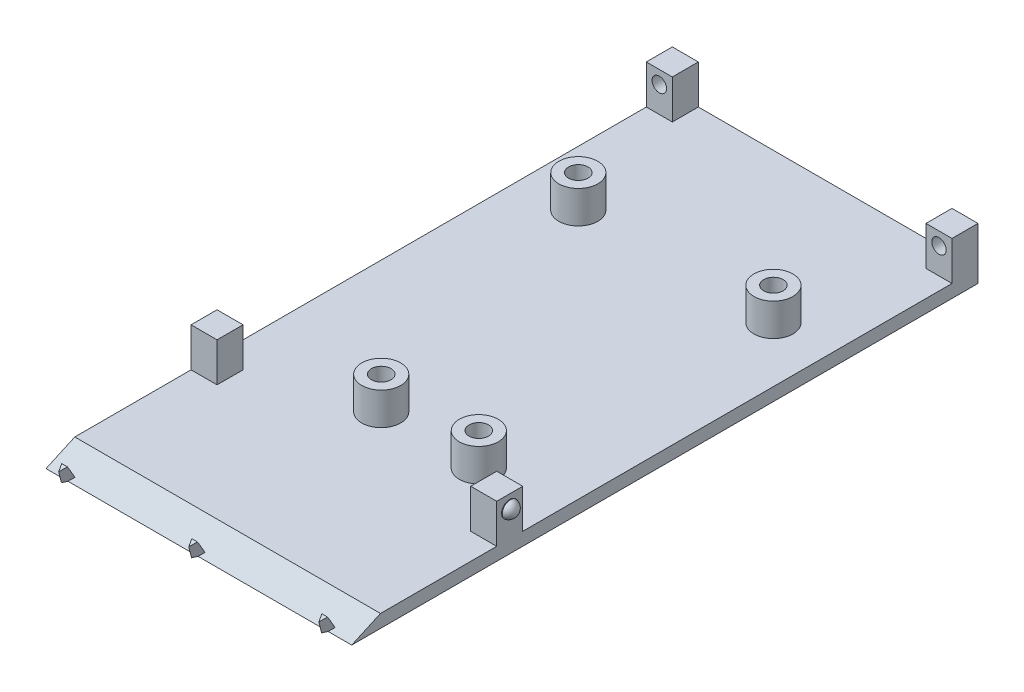
SolidWorks part; units mm, degrees
ref_plane "Ön Düzlem" through (0, 0, 0) normal (0, 0, 1) x (1, 0, 0)
ref_plane "Üst Düzlem" through (0, 0, 0) normal (0, 1, 0) x (1, 0, 0)
ref_plane "Sağ Düzlem" through (0, 0, 0) normal (1, 0, 0) x (0, 0, -1)
sketch "Çizim1" plane through (0, 0, 0) normal (0, 1, 0) x (1, 0, 0)
  line L1 (-23.5, 48.15) -> (23.5, 48.15)
  line L2 (-23.5, 48.15) -> (-23.5, -48.15)
  line L3 (-23.5, -48.15) -> (23.5, -48.15)
  line L4 (23.5, 48.15) -> (23.5, -48.15)
  line L5 (-23.5, 48.15) -> (23.5, -48.15) construction
  line L6 (-23.5, -48.15) -> (23.5, 48.15) construction
  point P0 (0, 0)
  dimension "D1" = 96.3
  dimension "D2" = 47
extrude "Yükseklik-Ekstrüzyon1" add sketch "Çizim1" along normal blind 2
sketch "Çizim2" plane through (-23.5, 0, 0) normal (-1, 0, 0) x (0, 0, 1)
  line L0 (48.15, 0) -> (43.7226, 2)
  line L1 (-48.15, 2) -> (48.15, 2) construction
  line L2 (43.7226, 2) -> (48.15, 2)
  line L3 (48.15, 2) -> (48.15, 0)
extrude "Kes-Ekstrüzyon1" cut sketch "Çizim2" against normal through all
sketch "Çizim3" plane through (0, 2, 0) normal (0, 1, 0) x (1, 0, 0)
  arc A8 (10.2, -16.8055) -> (13.2, -16.8055) centre (11.7, -16.8055) ccw
  arc A9 (13.2, -16.8055) -> (10.2, -16.8055) centre (11.7, -16.8055) ccw
  arc A10 (-1.8, -16.8055) -> (-4.8, -16.8055) centre (-3.3, -16.8055) ccw
  arc A11 (-4.8, -16.8055) -> (-1.8, -16.8055) centre (-3.3, -16.8055) ccw
  arc A12 (13.5, 25.1945) -> (16.5, 25.1945) centre (15, 25.1945) ccw
  arc A13 (16.5, 25.1945) -> (13.5, 25.1945) centre (15, 25.1945) ccw
  arc A14 (-16.5, 25.1945) -> (-13.5, 25.1945) centre (-15, 25.1945) ccw
  arc A15 (-13.5, 25.1945) -> (-16.5, 25.1945) centre (-15, 25.1945) ccw
  circle A16 centre (-15, 25.1945) radius 3
  circle A17 centre (15, 25.1945) radius 3
  circle A18 centre (-3.3, -16.8055) radius 3
  circle A19 centre (11.7, -16.8055) radius 3
  dimension "D1" = 6
extrude "Yükseklik-Ekstrüzyon2" add sketch "Çizim3" along normal blind 5
sketch "Çizim4" plane through (0, 18.0647, 8.1604) normal (0, 0.9113, 0.4117) x (1, 0, 0)
  line L9 (20.2234, -43.0729) -> (19.5734, -44.5624)
  line L10 (19.5734, -44.5624) -> (18.9234, -43.0729)
  line L11 (18.9234, -43.0729) -> (20.2234, -43.0729)
  line L12 (0.2234, -43.0729) -> (-0.4266, -44.5624)
  line L13 (-0.4266, -44.5624) -> (-1.0766, -43.0729)
  line L14 (-1.0766, -43.0729) -> (0.2234, -43.0729)
  line L15 (-21.0766, -43.0729) -> (-19.7766, -43.0729)
  line L16 (-20.4266, -44.5624) -> (-21.0766, -43.0729)
  line L17 (-19.7766, -43.0729) -> (-20.4266, -44.5624)
extrude "Yükseklik-Ekstrüzyon3" add sketch "Çizim4" along normal blind 2 draft 4
sketch "Çizim5" plane through (0, 0, 0) normal (0, -1, 0) x (1, 0, 0)
  line L1 (-23.5, 48.15) -> (23.5, 48.15)
  line L2 (-23.5, 48.15) -> (-23.5, 50.6467)
  line L3 (-23.5, 50.6467) -> (23.5, 50.6467)
  line L4 (23.5, 48.15) -> (23.5, 50.6467)
extrude "Kes-Ekstrüzyon3" cut sketch "Çizim5" along normal blind 4
sketch "Çizim6" plane through (0, 2, 0) normal (0, 1, 0) x (1, 0, 0)
  line L0 (0, 51.8826) -> (0, -64.1065) construction
  line L1 (-23.5, 48.15) -> (-19.5, 48.15)
  line L2 (-23.5, 48.15) -> (-23.5, 44.15)
  line L3 (-23.5, 44.15) -> (-19.5, 44.15)
  line L4 (-19.5, 48.15) -> (-19.5, 44.15)
  line L5 (19.5, 48.15) -> (19.5, 44.15)
  line L6 (23.5, 44.15) -> (19.5, 44.15)
  line L7 (23.5, 48.15) -> (23.5, 44.15)
  line L8 (23.5, 48.15) -> (19.5, 48.15)
  line L9 (-23.5, -21.85) -> (-19.5, -21.85)
  line L10 (-23.5, -21.85) -> (-23.5, -25.85)
  line L11 (-23.5, -25.85) -> (-19.5, -25.85)
  line L12 (-19.5, -21.85) -> (-19.5, -25.85)
  line L13 (19.5, -21.85) -> (19.5, -25.85)
  line L14 (23.5, -25.85) -> (19.5, -25.85)
  line L15 (23.5, -21.85) -> (23.5, -25.85)
  line L16 (23.5, -21.85) -> (19.5, -21.85)
  dimension "D3" = 2
  dimension "D1" = 4
  dimension "D2" = 4
extrude "Yükseklik-Ekstrüzyon4" add sketch "Çizim6" along normal blind 6
sketch "Çizim7" plane through (0, 0, -48.15) normal (0, 0, -1) x (-1, 0, 0)
  line L0 (-23.5, 8) -> (-19.5, 8) construction
  line L1 (0, 15.2383) -> (0, -10.9748) construction
  circle A0 centre (-21.5, 6) radius 1.25
  circle A1 centre (21.5, 6) radius 1.25
  dimension "D1" = 2.5
  dimension "D2" = 2
extrude "Kes-Ekstrüzyon4" cut sketch "Çizim7" against normal blind 4 draft 2
sketch "Çizim8" plane through (-23.5, 0, 0) normal (-1, 0, 0) x (0, 0, 1)
  line L0 (21.85, 8) -> (25.85, 8) construction
  circle A0 centre (23.85, 6) radius 1.25
  dimension "D1" = 2.5
  dimension "D2" = 2
extrude "Yükseklik-Ekstrüzyon5" add sketch "Çizim8" along normal blind 0.1 contours A0
dome "Kubbe5" faces to dome 1 distance 1 reverse direction no elliptical dome no face at (-23.6, 6, 25.1) parameters "D1"=1
mirror "Aynalama8" about plane through (0, 0, 0) normal (1, 0, 0) of "Kubbe5", "Yükseklik-Ekstrüzyon5"
